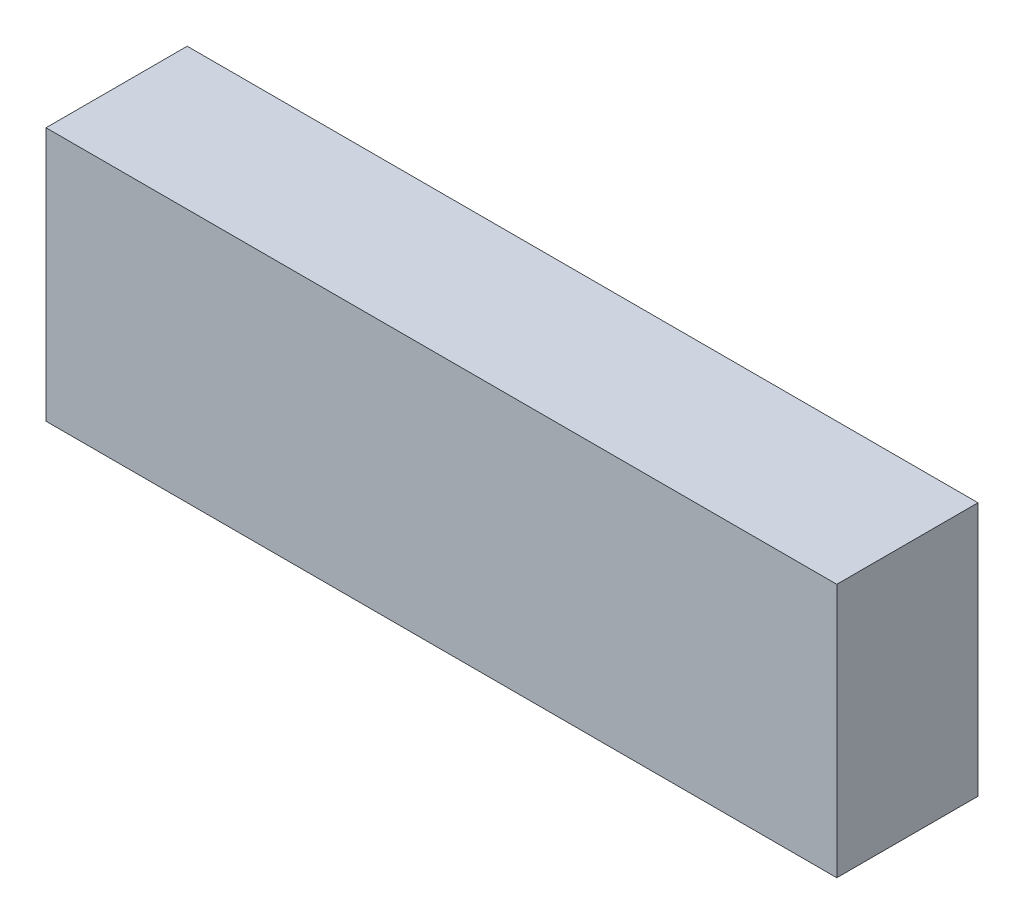
SolidWorks part; units mm, degrees
ref_plane "Front Plane" through (0, 0, 0) normal (0, 0, 1) x (1, 0, 0)
ref_plane "Top Plane" through (0, 0, 0) normal (0, 1, 0) x (1, 0, 0)
ref_plane "Right Plane" through (0, 0, 0) normal (1, 0, 0) x (0, 0, -1)
sketch "Sketch1" plane through (0, 0, 0) normal (0, 0, 1) x (1, 0, 0)
  line L1 (0, 0) -> (140, 0)
  line L2 (0, 0) -> (0, 45)
  line L3 (0, 45) -> (140, 45)
  line L4 (140, 0) -> (140, 45)
  dimension "D1" = 140
  dimension "D2" = 45
extrude "Boss-Extrude1" add sketch "Sketch1" along normal blind 25
extrude "Boss-Extrude2" add sketch "Sketch1<3>" along normal blind 12.5
sketch "Sketch1<3>" plane through (0, 0, 0) normal (0, 0, 1) x (1, 0, 0) same geometry as "Sketch1"
